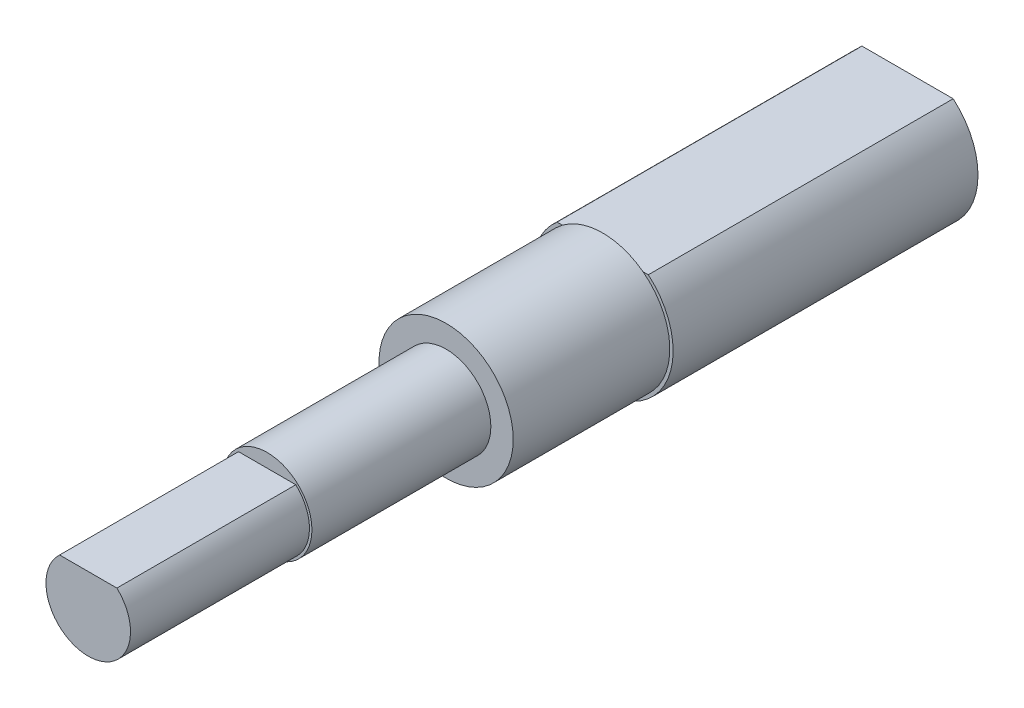
SolidWorks part; units mm, degrees
material "1060 Alloy"
ref_plane "Front" through (0, 0, 0) normal (0, 0, 1) x (1, 0, 0)
ref_plane "Top" through (0, 0, 0) normal (0, 1, 0) x (1, 0, 0)
ref_plane "Right" through (0, 0, 0) normal (1, 0, 0) x (0, 0, -1)
sketch "Sketch1" plane through (0, 0, 0) normal (0, 0, 1) x (1, 0, 0)
  circle A0 centre (0, 0) radius 5
  dimension "D1" = 10
extrude "Boss-Extrude1" add sketch "Sketch1" along normal blind 21.6375
sketch "Sketch2" plane through (0, 0, 21.6375) normal (0, 0, 1) x (1, 0, 0)
  circle A0 centre (0, 0) radius 4.7625
  dimension "D1" = 9.525
extrude "Boss-Extrude2" add sketch "Sketch2" along normal blind 11.1125
sketch "Sketch3" plane through (0, 0, 32.75) normal (0, 0, 1) x (1, 0, 0)
  circle A0 centre (0, 0) radius 3.175
  dimension "D1" = 6.35
extrude "Boss-Extrude3" add sketch "Sketch3" along normal blind 12.7
sketch "Sketch4" plane through (0, 0, 0) normal (0, 0, -1) x (-1, 0, 0)
  line L0 (0, 0) -> (0, 5) construction
  line L2 (12.7, 3.8094) -> (-12.7, 3.8094)
  line L3 (12.7, 3.8094) -> (12.7, 6.1906)
  line L4 (12.7, 6.1906) -> (-12.7, 6.1906)
  line L5 (-12.7, 3.8094) -> (-12.7, 6.1906)
  line L6 (12.7, 3.8094) -> (-12.7, 6.1906) construction
  line L7 (12.7, 6.1906) -> (-12.7, 3.8094) construction
  circle A0 centre (0, 0) radius 5 construction
  dimension "D1" = 2.3813
  dimension "D2" = 25.4
extrude "Cut-Extrude1" cut sketch "Sketch4" against normal up to surface (21.6375 mm away) up to face at (4.7625, 0, 21.6375)
sketch "Sketch5" plane through (0, 0, 45.45) normal (0, 0, 1) x (1, 0, 0)
  line L0 (0, 0) -> (0, 3.175) construction
  line L2 (12.7, 2.3813) -> (-12.7, 2.3812)
  line L3 (12.7, 2.3813) -> (12.7, 3.9688)
  line L4 (12.7, 3.9688) -> (-12.7, 3.9687)
  line L5 (-12.7, 2.3812) -> (-12.7, 3.9687)
  line L6 (12.7, 2.3813) -> (-12.7, 3.9687) construction
  line L7 (12.7, 3.9688) -> (-12.7, 2.3812) construction
  circle A0 centre (0, 0) radius 3.175 construction
  dimension "D1" = 1.5875
  dimension "D2" = 25.4
sketch "Sketch6" plane through (0, 0, 45.45) normal (0, 0, 1) x (1, 0, 0)
  circle A0 centre (0, 0) radius 3
  dimension "D1" = 6
extrude "Boss-Extrude4" add sketch "Sketch6" along normal blind 12.7
sketch "Sketch7" plane through (0, 0, 58.15) normal (0, 0, 1) x (1, 0, 0)
  line L0 (0, 0) -> (0, 3) construction
  line L2 (12.6863, 2.2063) -> (-12.6863, 2.2062)
  line L3 (12.6863, 2.2063) -> (12.6863, 3.7938)
  line L4 (12.6863, 3.7938) -> (-12.6863, 3.7937)
  line L5 (-12.6863, 2.2062) -> (-12.6863, 3.7937)
  line L6 (12.6863, 2.2063) -> (-12.6863, 3.7937) construction
  line L7 (12.6863, 3.7938) -> (-12.6863, 2.2062) construction
  circle A0 centre (0, 0) radius 3 construction
  dimension "D1" = 1.5875
  dimension "D2" = 25.3725
extrude "Cut-Extrude3" cut sketch "Sketch7" against normal up to surface (12.7 mm away) up to face at (3, 0, 45.45)
